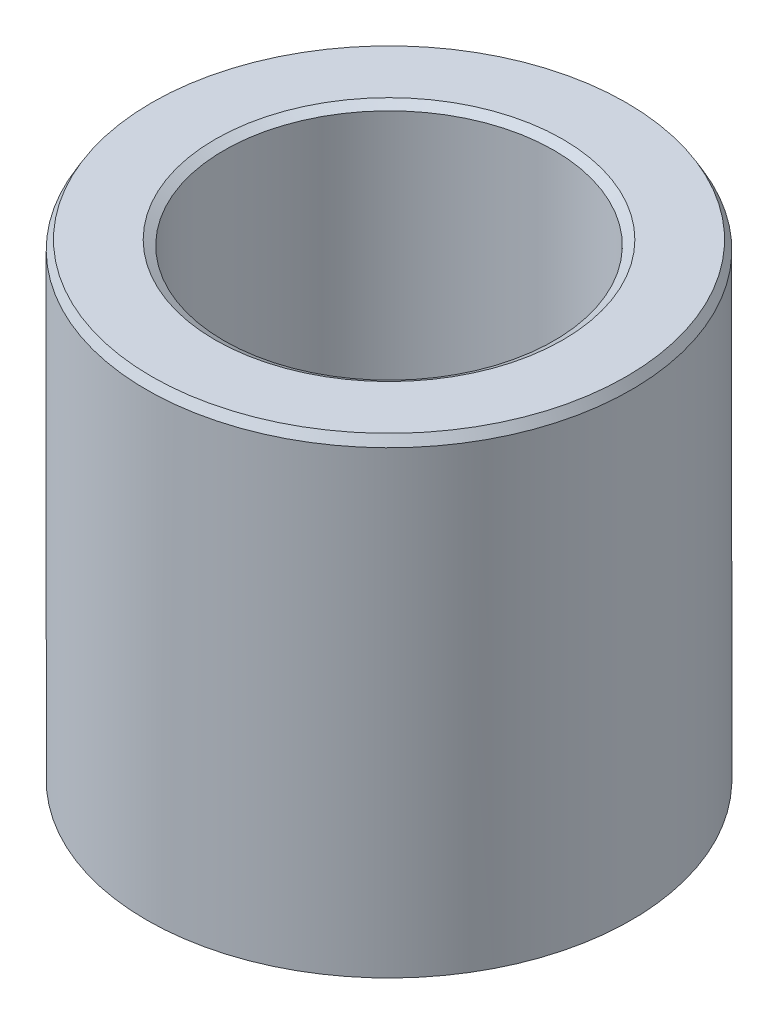
SolidWorks part; units mm, degrees
ref_plane "Front Plane" through (0, 0, 0) normal (0, 0, 1) x (1, 0, 0)
ref_plane "Top Plane" through (0, 0, 0) normal (0, 1, 0) x (1, 0, 0)
ref_plane "Right Plane" through (0, 0, 0) normal (1, 0, 0) x (0, 0, -1)
sketch "Sketch1" plane through (0, 0, 0) normal (0, 1, 0) x (1, 0, 0)
  circle A0 centre (0, 0) radius 60
  dimension "SLEEVE_OD" = 120
extrude "Boss-Extrude1" add sketch "Sketch1" along normal blind 117.1267
sketch "Sketch2" plane through (0, 0, 0) normal (0, 1, 0) x (1, 0, 0)
  circle A0 centre (0, 0) radius 40.8351
  dimension "BORE_D" = 81.6702
extrude "Cut-Extrude1" cut sketch "Sketch2" along normal through all
chamfer "Chamfer1" distance 2.196 angle 30 4 edges at (0, 117.1267, 40.8351) (0, 0, 40.8351) (0, 0, 60) (0, 117.1267, 60) first distance on face at (0, 117.1267, 40.8351) first distance on face at (0, 0, 40.8351) first distance on face at (0, 117.1267, 60)
